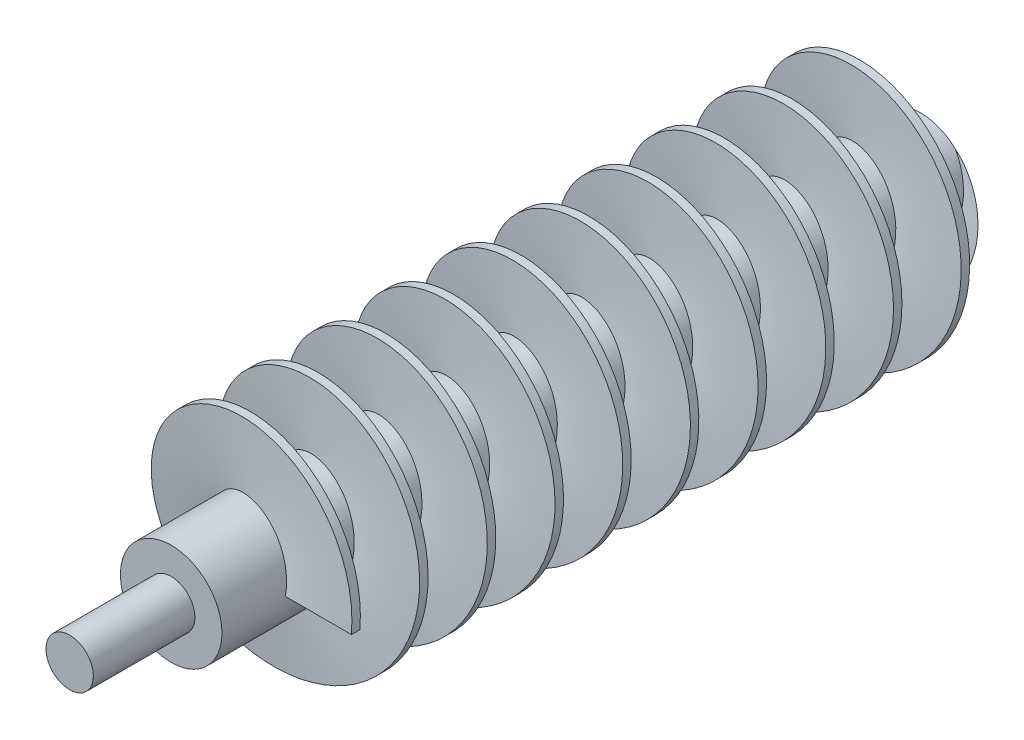
SolidWorks part; units mm, degrees
material "AISI 304"
ref_plane "Спереди" through (0, 0, 0) normal (0, 0, 1) x (1, 0, 0)
ref_plane "Сверху" through (0, 0, 0) normal (0, 1, 0) x (1, 0, 0)
ref_plane "Справа" through (0, 0, 0) normal (1, 0, 0) x (0, 0, -1)
ref_plane "Плоскость1" through (0, 0, -17) normal (0, 0, 1) x (1, 0, 0)
sketch "Эскиз1" plane through (0, 0, 0) normal (0, 0, 1) x (1, 0, 0)
  circle A0 centre (0, 0) radius 15
  dimension "D1" = 30
sketch "Эскиз2" plane through (0, 0, 0) normal (0, 1, 0) x (1, 0, 0)
  line L0 (15, 0) -> (-4.9813, 0) construction
  line L1 (15, 1.25) -> (34.5, 1.25)
  line L2 (15, 1.25) -> (15, -1.25)
  line L3 (15, -1.25) -> (34.5, -1.25)
  line L4 (34.5, 1.25) -> (34.5, -1.25)
  dimension "D1" = 2.5
  dimension "D2" = 15
  dimension "D3" = 34.5
curve "Спираль1" pitch 20 height 210 radius 15 left hand yes centre (0, 0, 0) axis (0, 0, -1) start towards (1, 0, 0)
sweep "По траектории1" add profiles "Эскиз2" path "Спираль1"
sketch "Эскиз3" plane through (0, 0, 0) normal (0, 1, 0) x (1, 0, 0)
  line L0 (0, -50) -> (7, -50)
  line L1 (7, -50) -> (7, -20)
  line L2 (7, -20) -> (15, -20)
  line L3 (15, -20) -> (15, 210)
  line L4 (15, 210) -> (0, 210)
  line L5 (0, 210) -> (0, -50)
  line L6 (0, -59.6319) -> (0, 170.3599) construction
  dimension "D1" = 260
  dimension "D2" = 50
  dimension "D3" = 30
  dimension "D4" = 14
revolve "Повернуть1" add sketch "Эскиз3" angle 360 mid plane about L6
sketch "Эскиз4" plane through (0, 0, 0) normal (0, -1, 0) x (0, 0, -1)
  line L0 (274.0709, 0) -> (145.9291, 0) construction
  line L2 (211.25, 0) -> (211.25, 34.5)
  line L3 (211.25, 34.5) -> (190.0814, 34.5)
  line L5 (211.25, 0) -> (210, 0)
  line L6 (210, 0) -> (190.0814, 34.5)
  line L7 (210, -15) -> (210, 15) construction
  dimension "D1" = 60
revolve "Вырез-Повернуть1" cut sketch "Эскиз4" angle 360 mid plane about L0
